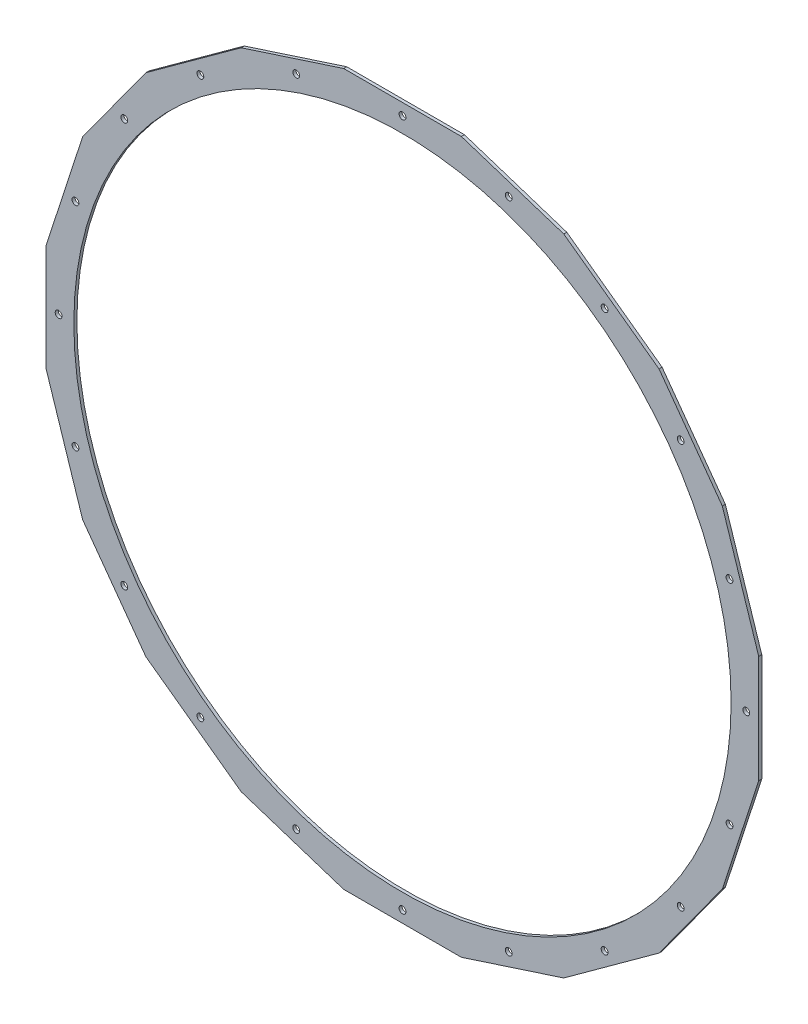
SolidWorks part; units mm, degrees
note: '?' marks a value the reader was unsure of.
material "Plain Carbon Steel"
ref_plane "Front" through (0, 0, 0) normal (0, 0, 1) x (1, 0, 0)
ref_plane "Top" through (0, 0, 0) normal (0, 1, 0) x (1, 0, 0)
ref_plane "Right" through (0, 0, 0) normal (1, 0, 0) x (0, 0, -1)
sketch "Sketch1" plane through (0, 0, 0) normal (0, 0, 1) x (1, 0, 0)
  circle A0 centre (0, 0) radius 375.92
  circle A1 centre (0, 0) radius 342.9
  dimension "D1" = 751.84
  dimension "D2" = 685.8
extrude "Extrude1" add sketch "Sketch1" along normal blind 3.175
ref_plane "Plane1" through (0, 0, 373.3022) normal (0, 0, 1) x (1, 0, 0)
sketch "Sketch2" plane through (0, 0, 3.175) normal (0, 0, 1) x (1, 0, 0)
  line L1 (0, 0) -> (0, -358.775) construction
  line L2 (0, 0) -> (0, -358.775) construction
  circle A0 centre (0, 0) radius 358.775 construction
  circle A1 centre (0, -358.775) radius 3.556
  dimension "D1" = 717.55
  dimension "D3" = 7.112
  dimension "D2" = 0
extrude "Cut-Extrude1" cut sketch "Sketch2" against normal up to next
ref_axis "Axis1" through (0, 0, -98.3996) along (0, 0, 1)?
pattern_circular "CirPattern1" count 20 over 360 about axis through (0, 0, 0) along (0, 0, 1) of "Cut-Extrude1"
sketch "Sketch3" plane through (0, 0, 3.175) normal (0, 0, 1) x (1, 0, 0)
  line L0 (168.2947, -336.1439) -> (61.4269, -370.8673)
  line L1 (61.4269, -370.8673) -> (-61.4271, -370.8673)
  line L2 (61.4269, -370.8673) -> (0, 0) construction
  line L3 (-61.4271, -370.8673) -> (0, 0) construction
  line L4 (0, 0) -> (168.2947, -336.1439) construction
  line L5 (-61.4271, -370.8673) -> (-80.5875, -486.548)
  line L6 (168.2947, -336.1439) -> (220.7891, -440.9937)
  line L7 (-80.5875, -486.548) -> (220.7891, -440.9937)
  circle A0 centre (0, 0) radius 375.92 construction
  dimension "D1" = 304.8
extrude "Cut-Extrude3" cut sketch "Sketch3" against normal up to next
pattern_circular "CirPattern2" count 10 over 360 about axis through (0, 0, 0) along (0, 0, 1) of "Cut-Extrude3"
fillet "Fillet1" [suppressed] radius 9.525
